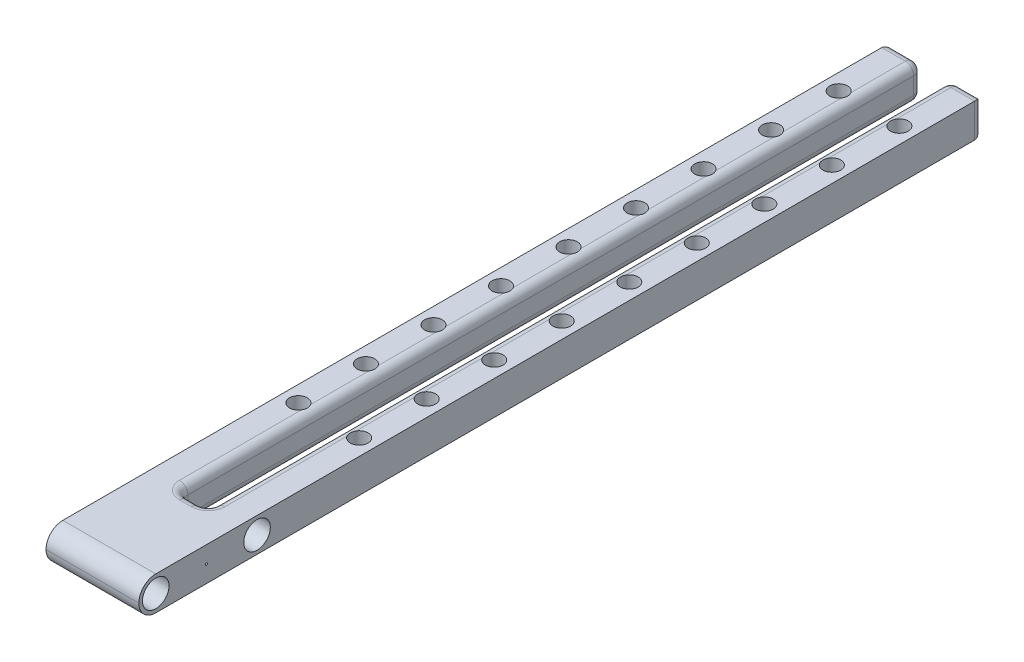
SolidWorks part; units mm, degrees
ref_plane "Front Plane" through (0, 0, 0) normal (0, 0, 1) x (1, 0, 0)
ref_plane "Top Plane" through (0, 0, 0) normal (0, 1, 0) x (1, 0, 0)
ref_plane "Right Plane" through (0, 0, 0) normal (1, 0, 0) x (0, 0, -1)
sketch "Sketch1" plane through (0, 0, 0) normal (0, 1, 0) x (1, 0, 0)
  line L0 (0, 0) -> (22, 0)
  line L1 (22, 0) -> (22, 200)
  line L2 (22, 200) -> (14.4, 200)
  line L3 (14.4, 200) -> (14.4, 24)
  line L4 (14.4, 24) -> (7.6, 24)
  line L5 (7.6, 24) -> (7.6, 200)
  line L6 (7.6, 200) -> (0, 200)
  line L7 (0, 200) -> (0, 0)
  line L8 (3.8, 184) -> (18.2, 184) construction
  circle A0 centre (3.8, 184) radius 2.1
  circle A1 centre (18.2, 184) radius 2.1
  circle A2 centre (3.8, 168) radius 2.1
  circle A3 centre (18.2, 168) radius 2.1
  circle A4 centre (3.8, 152) radius 2.1
  circle A5 centre (18.2, 152) radius 2.1
  circle A6 centre (3.8, 136) radius 2.1
  circle A7 centre (18.2, 136) radius 2.1
  circle A8 centre (3.8, 120) radius 2.1
  circle A9 centre (18.2, 120) radius 2.1
  circle A10 centre (3.8, 104) radius 2.1
  circle A11 centre (18.2, 104) radius 2.1
  circle A12 centre (3.8, 88) radius 2.1
  circle A13 centre (18.2, 88) radius 2.1
  circle A14 centre (3.8, 72) radius 2.1
  circle A15 centre (18.2, 72) radius 2.1
  circle A16 centre (3.8, 56) radius 2.1
  circle A17 centre (18.2, 56) radius 2.1
  dimension "D5" = 4.2
  dimension "D6" = 4.2
  dimension "D1" = 22
  dimension "D2" = 200
  dimension "D3" = 24
  dimension "D4" = 7.6
  dimension "D7" = 3.8
  dimension "D8" = 16
  dimension "D9" = 3.8
  dimension "D11" = 6.8
  dimension "D10" = 9
extrude "Boss-Extrude1" add sketch "Sketch1" along normal blind 8
sketch "Sketch2" plane through (0, 0, 0) normal (-1, 0, 0) x (0, 0, 1)
  line L0 (0, 8) -> (0, 0) construction
  line L1 (-200, 0) -> (0, 0) construction
  circle A0 centre (-28, 4) radius 3.15
  circle A1 centre (-4, 4) radius 3.15
  point P6 (104.8353, 4.5913)
  dimension "D1" = 6.3
  dimension "D2" = 6.3
  dimension "D3" = 24
  dimension "D4" = 4
  dimension "D5" = 4
  dimension "D6" = 4
extrude "Cut-Extrude1" cut sketch "Sketch2" against normal blind 4.7
sketch "Sketch3" plane through (22, 0, 0) normal (1, 0, 0) x (0, 0, -1)
  line L0 (4, 4) -> (28, 4) construction
  circle A0 centre (4, 4) radius 3.15
  circle A1 centre (28, 4) radius 3.15
  circle A2 centre (16, 4) radius 0.25
  dimension "D1" = 6.3
  dimension "D2" = 6.3
  dimension "D3" = 0.5
extrude "Cut-Extrude2" cut sketch "Sketch3" against normal blind 4.7
fillet "Fillet1" radius 4 2 edges at (11, 0, 0) (11, 8, 0)
fillet "Fillet2" radius 2 16 edges at (7.6, 4, -24) (14.4, 4, -24) (0, 4, -200) (7.6, 4, -200) (14.4, 4, -200) (22, 4, -200) (7.6, 0, -112) (7.6, 8, -112) (11, 0, -24) (11, 8, -24) (18.2, 0, -200) (3.8, 0, -200) (18.2, 8, -200) (3.8, 8, -200) (14.4, 0, -112) (14.4, 8, -112)
